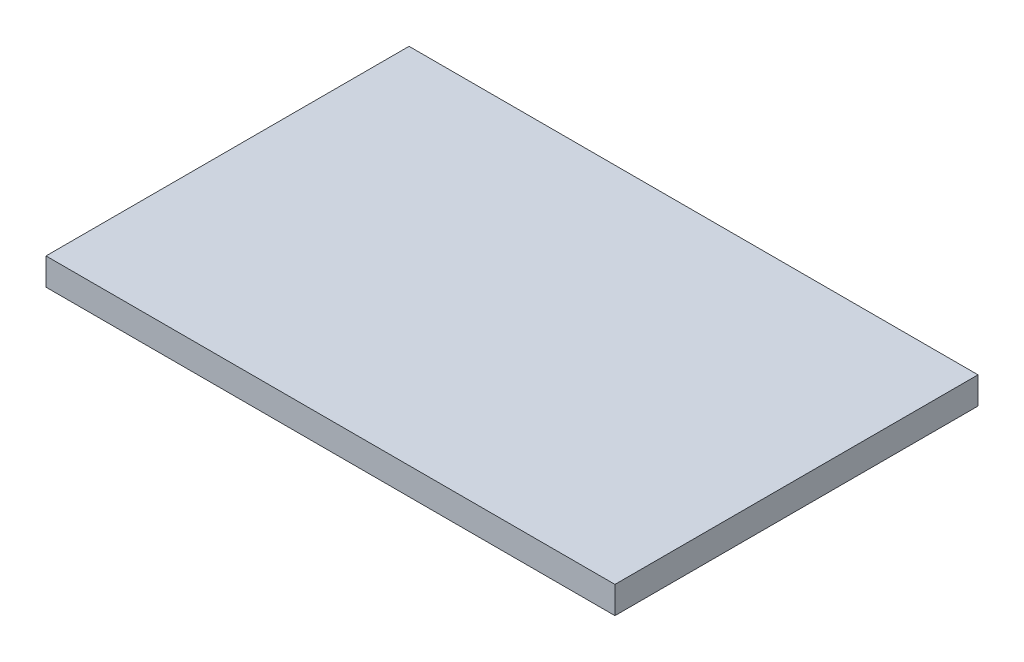
SolidWorks part; units mm, degrees
material "AISI Type A2 Tool Steel"
ref_plane "Front Plane" through (0, 0, 0) normal (0, 0, 1) x (1, 0, 0)
ref_plane "Top Plane" through (0, 0, 0) normal (0, 1, 0) x (1, 0, 0)
ref_plane "Right Plane" through (0, 0, 0) normal (1, 0, 0) x (0, 0, -1)
sketch "Sketch1" plane through (0, 0, 0) normal (0, 1, 0) x (1, 0, 0)
  line L1 (-45.1884, 47.6545) -> (88.1616, 47.6545)
  line L2 (-45.1884, 47.6545) -> (-45.1884, -37.4355)
  line L3 (-45.1884, -37.4355) -> (88.1616, -37.4355)
  line L4 (88.1616, 47.6545) -> (88.1616, -37.4355)
  dimension "D1" = 133.35
  dimension "D2" = 85.09
extrude "Boss-Extrude1" add sketch "Sketch1" along normal blind 6.35
